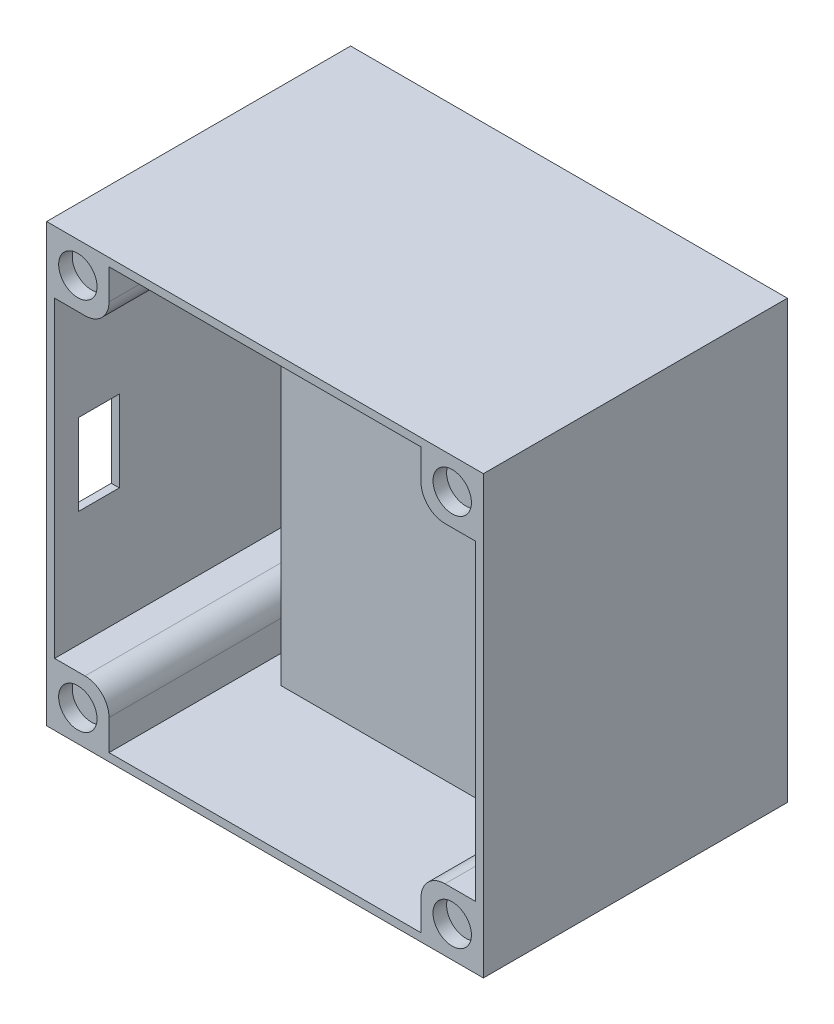
SolidWorks part; units mm, degrees
ref_plane "Přední rovina" through (0, 0, 0) normal (0, 0, 1) x (1, 0, 0)
ref_plane "Horní rovina" through (0, 0, 0) normal (0, 1, 0) x (1, 0, 0)
ref_plane "Pravá rovina" through (0, 0, 0) normal (1, 0, 0) x (0, 0, -1)
sketch "Skica1" plane through (0, 0, 0) normal (0, 0, 1) x (1, 0, 0)
  line L1 (27.3, 27.3) -> (-27.3, 27.3)
  line L2 (27.3, 27.3) -> (27.3, -27.3)
  line L3 (27.3, -27.3) -> (-27.3, -27.3)
  line L4 (-27.3, 27.3) -> (-27.3, -27.3)
  line L5 (27.3, 27.3) -> (-27.3, -27.3) construction
  line L6 (27.3, -27.3) -> (-27.3, 27.3) construction
  point P0 (0, 0)
  point P5 (-27.5, 0)
  point P11 (4.5, 0)
  dimension "D1" = 54.6
  dimension "D2" = 54.6
extrude "Přidat vysunutím2" add sketch "Skica1" along normal blind 3 contours L2 L1 L4 L3
sketch "Skica14" plane through (0, 0, 3) normal (0, 0, 1) x (1, 0, 0)
  line L1 (-27.3, 27.3) -> (27.3, 27.3)
  line L2 (-27.3, 27.3) -> (-27.3, -27.3)
  line L3 (-27.3, -27.3) -> (27.3, -27.3)
  line L4 (27.3, 27.3) -> (27.3, -27.3)
  line L5 (-26.3, 26.3) -> (26.3, 26.3)
  line L6 (-26.3, 26.3) -> (-26.3, -27.3)
  line L7 (-26.3, -27.3) -> (26.3, -27.3)
  line L8 (26.3, 26.3) -> (26.3, -27.3)
  line L9 (-26.3, -27.3) -> (26.3, -27.3)
  line L10 (-26.3, -27.3) -> (-26.3, -26.3)
  line L11 (-26.3, -26.3) -> (26.3, -26.3)
  line L12 (26.3, -27.3) -> (26.3, -26.3)
  line M13 (-27.3, -27.3) -> (27.3, -27.3)
  line M14 (27.3, -27.3) -> (27.3, 27.3)
  line M15 (27.3, 27.3) -> (-27.3, 27.3)
  line M16 (-27.3, 27.3) -> (-27.3, -27.3)
  dimension "D1" = 1
  dimension "D2" = 1
  dimension "D3" = 1
  dimension "D4" = 0
  dimension "D5" = 1
  dimension "D6" = 52.6
extrude "Přidat vysunutím9" add sketch "Skica14" along normal blind 35 contours L5 L8 L6 M13 M14 M15 M16 | L10 L9 L12 L11 region at (0, 26.5278, 3)
sketch "Skica19" plane through (0, 0, 0) normal (0, 0, -1) x (-1, 0, 0)
  line L1 (-27.3, 27.3) -> (-19.5, 27.3)
  line L2 (-27.3, 27.3) -> (-27.3, 19.5)
  line L3 (-27.3, 19.5) -> (-19.5, 19.5)
  line L4 (-19.5, 27.3) -> (-19.5, 19.5)
  line L5 (27.3, 27.3) -> (19.5, 27.3)
  line L6 (27.3, 27.3) -> (27.3, 19.5)
  line L7 (27.3, 19.5) -> (19.5, 19.5)
  line L8 (19.5, 27.3) -> (19.5, 19.5)
  line L9 (-27.3, -27.3) -> (-19.5, -27.3)
  line L10 (-27.3, -27.3) -> (-27.3, -19.5)
  line L11 (-27.3, -19.5) -> (-19.5, -19.5)
  line L12 (-19.5, -27.3) -> (-19.5, -19.5)
  line L13 (27.3, -27.3) -> (19.5, -27.3)
  line L14 (27.3, -27.3) -> (27.3, -19.5)
  line L15 (27.3, -19.5) -> (19.5, -19.5)
  line L16 (19.5, -27.3) -> (19.5, -19.5)
  dimension "D1" = 7.8
  dimension "D2" = 7.8
  dimension "D3" = 7.8
  dimension "D4" = 7.8
extrude "Přidat vysunutím10" add sketch "Skica19" against normal blind 38
sketch "Skica20" plane through (0, 0, 38) normal (0, 0, 1) x (1, 0, 0)
  line L0 (-27.3, -27.3) -> (27.3, -27.3) construction
  line L1 (-19.5, -26.3) -> (-19.5, -19.5) construction
  line L2 (-27.3, 27.3) -> (-27.3, -27.3) construction
  line L3 (27.3, 27.3) -> (-27.3, 27.3) construction
  line L4 (27.3, -27.3) -> (27.3, 27.3) construction
  line L5 (-27.3, -27.3) -> (27.3, -27.3) construction
  circle A0 centre (-23.4, -23.4) radius 2.4
  circle A1 centre (-23.4, 23.4) radius 2.4
  circle A2 centre (23.4003, 23.4) radius 2.4
  circle A3 centre (23.4003, -23.4) radius 2.4
  dimension "D1" = 4.8
  dimension "D4" = 4.8
  dimension "D5" = 3.9
  dimension "D7" = 4.8
  dimension "D10" = 4.8
  dimension "D2" = 3.9
  dimension "D3" = 3.9
  dimension "D6" = 3.9
  dimension "D8" = 3.8997
  dimension "D9" = 3.9
  dimension "D11" = 3.9
  dimension "D12" = 3.8997
extrude "Odebrat vysunutím9" cut sketch "Skica20" against normal blind 1.7
fillet "Zaoblit1" radius 3 4 edges at (19.5, 19.5, 20.5) (19.5, -19.5, 20.5) (-19.5, -19.5, 20.5) (-19.5, 19.5, 20.5)
sketch "Skica25" plane through (0, 0, 0) normal (0, 0, -1) x (-1, 0, 0)
  line L0 (27.3, 27.3) -> (27.3, -27.3) construction
  line L1 (16, 27.3) -> (-16, 27.3)
  line L2 (16, 27.3) -> (16, -27.3)
  line L3 (16, -27.3) -> (-16, -27.3)
  line L4 (-16, 27.3) -> (-16, -27.3)
  line L5 (-27.3, 27.3) -> (27.3, 27.3) construction
  dimension "D1" = 54.6
  dimension "D2" = 32
  dimension "D3" = 11.3
  dimension "D4" = 0
extrude "Přidat vysunutím12" add sketch "Skica25" against normal blind 20
sketch "Skica26" plane through (0, 0, 0) normal (0, 0, -1) x (-1, 0, 0)
  line L0 (-27.3, 27.3) -> (-27.3, -27.3) construction
  line L1 (-15, 26) -> (15, 26)
  line L2 (-15, 26) -> (-15, -26)
  line L3 (-15, -26) -> (15, -26)
  line L4 (15, 26) -> (15, -26)
  line L5 (-27.3, 27.3) -> (27.3, 27.3) construction
  dimension "D1" = 52
  dimension "D2" = 30
  dimension "D3" = 12.3
  dimension "D4" = 1.3
extrude "Odebrat vysunutím11" cut sketch "Skica26" against normal blind 19
sketch "Skica27" plane through (-27.3, 0, 0) normal (-1, 0, 0) x (0, 0, 1)
  line L0 (38, 27.3) -> (0, 27.3) construction
  line L1 (35, 5.08) -> (29.92, 5.08)
  line L2 (35, 5.08) -> (35, -5.08)
  line L3 (35, -5.08) -> (29.92, -5.08)
  line L4 (29.92, 5.08) -> (29.92, -5.08)
  line L5 (38, -27.3) -> (0, -27.3) construction
  line L6 (38, 27.3) -> (38, -27.3) construction
  dimension "D1" = 10.16
  dimension "D2" = 5.08
  dimension "D3" = 22.22
  dimension "D4" = 22.22
  dimension "D5" = 3
extrude "Odebrat vysunutím12" cut sketch "Skica27" against normal blind 1
sketch "Skica28" plane through (0, 0, 0) normal (0, 0, -1) x (-1, 0, 0)
  line L0 (-15, 26) -> (-15, -26) construction
  line L1 (-15, 20.9403) -> (-24, 20.9403)
  line L2 (-15, 20.9403) -> (-15, 12.9403)
  line L3 (-15, 12.9403) -> (-24, 12.9403)
  line L4 (-24, 20.9403) -> (-24, 12.9403)
  dimension "D1" = 8
  dimension "D2" = 9
extrude "Odebrat vysunutím13" cut sketch "Skica28" against normal blind 1
fillet "Zaoblit3" radius 4 2 edges at (24, 12.9403, 0.5) (24, 20.9403, 0.5)
sketch "Skica29" plane through (-15, 0, 0) normal (1, 0, 0) x (0, 0, -1)
  line L0 (0, -26) -> (0, 26) construction
  line L1 (-1, 21) -> (-0.5, 21)
  line L2 (-1, 21) -> (-1, 17)
  line L3 (-1, 17) -> (-0.5, 17)
  line L4 (-0.5, 21) -> (-0.5, 17)
  line L5 (-19, -26) -> (0, -26) construction
  line L6 (-1.08, -17) -> (-0.58, -17)
  line L7 (-1.08, -17) -> (-1.08, -21)
  line L8 (-1.08, -21) -> (-0.58, -21)
  line L9 (-0.58, -17) -> (-0.58, -21)
  line L10 (-19, 26) -> (0, 26) construction
  dimension "D1" = 4
  dimension "D2" = 0.5
  dimension "D3" = 0.5
  dimension "D4" = 4
  dimension "D5" = 0.5
  dimension "D6" = 0.58
  dimension "D7" = 5
  dimension "D8" = 5
extrude "Odebrat vysunutím14" cut sketch "Skica29" against normal blind 2
sketch "Skica30" plane through (0, 0, 1) normal (0, 0, -1) x (-1, 0, 0)
  circle A0 centre (-20, 16.9403) radius 0.9
  dimension "D1" = 1.8
  dimension "D2" = 4
  dimension "D3" = 4
extrude "Odebrat vysunutím15" cut sketch "Skica30" against normal blind 2
sketch "Skica31" plane through (0, 0, 19) normal (0, 0, -1) x (-1, 0, 0)
  line L1 (-15, 26) -> (-9, 26)
  line L2 (-15, 26) -> (-15, 22)
  line L3 (-15, 22) -> (-9, 22)
  line L4 (-9, 26) -> (-9, 22)
  dimension "D1" = 4
  dimension "D2" = 6
extrude "Odebrat vysunutím16" cut sketch "Skica31" against normal blind 2
fillet "Zaoblit4" radius 1 1 edges at (9, 22, 19.5)
